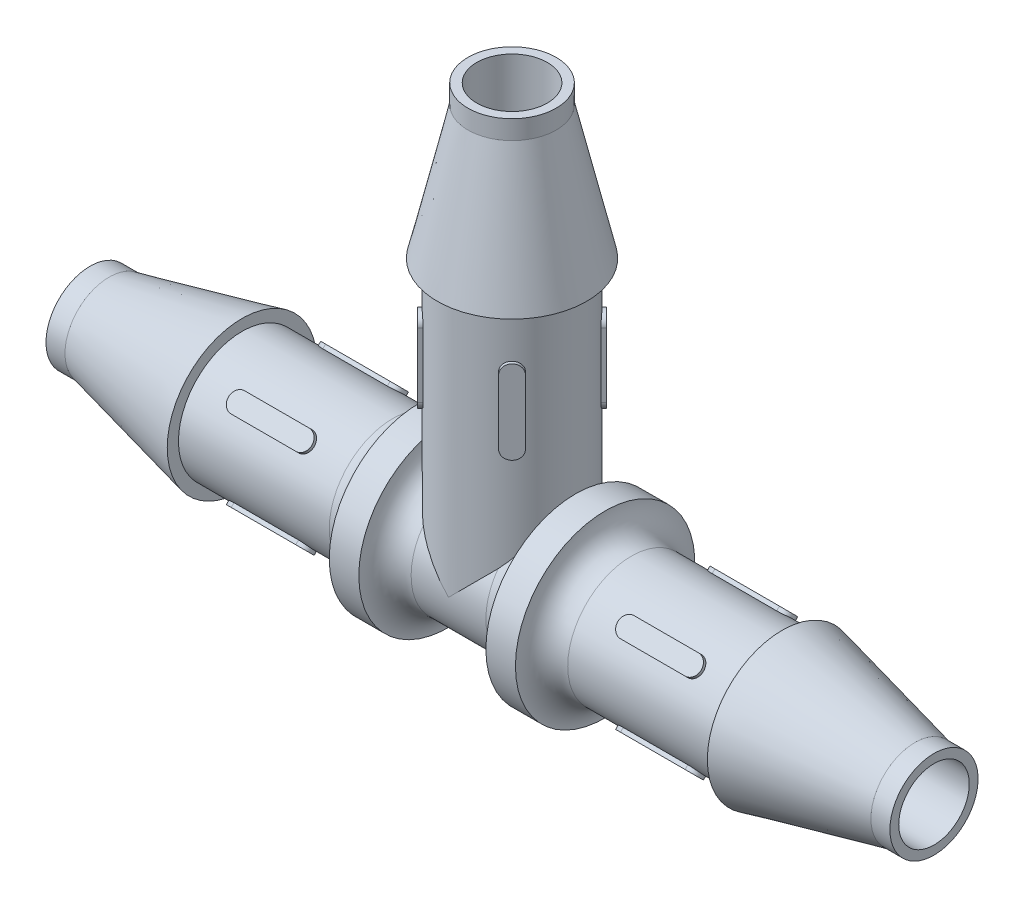
SolidWorks part; units mm, degrees
ref_plane "Front Plane" through (0, 0, 0) normal (0, 0, 1) x (1, 0, 0)
ref_plane "Top Plane" through (0, 0, 0) normal (0, 1, 0) x (1, 0, 0)
ref_plane "Right Plane" through (0, 0, 0) normal (1, 0, 0) x (0, 0, -1)
sketch "Sketch1" plane through (0, 0, 0) normal (0, 0, 1) x (1, 0, 0)
  line L0 (-17.78, 0) -> (17.78, 0) construction
  line L1 (17.78, 1.4859) -> (17.78, -1.4859) construction
  line L2 (17.78, 3.1496) -> (17.78, -3.1496) construction
  line L3 (17.78, 2.3812) -> (17.78, -2.3813) construction
  line L4 (0, 2.6772) -> (0, -2.6772) construction
  line L5 (0, -2.6772) -> (0, 17.4396) construction
  point P4 (0, 0)
  point P8 (17.78, 0)
  point P11 (17.78, 0)
  point P14 (17.78, 0)
  point P17 (0, 0)
  dimension "C" = 35.56
  dimension "A" = 2.9718
  dimension "B" = 6.2992
  dimension "For Tube ID" = 4.7625
  dimension "D1" = 5.3543
  dimension "D" = 20.1168
sketch "Sketch3" plane through (0, 0, 0) normal (0, 0, 1) x (1, 0, 0)
  line L0 (0, 0) -> (17.78, 0) construction
  line L1 (17.78, 1.4859) -> (17.78, 1.8574)
  line L2 (3.9218, -3.7795) -> (2.6772, -3.7795) construction
  line L3 (11.3792, 3.1496) -> (11.3792, 2.6772)
  line L4 (11.3792, 2.6772) -> (3.9218, 2.6772)
  line L5 (17.78, 1.8574) -> (16.9799, 1.8574)
  line L6 (3.9218, 2.6772) -> (3.9218, 3.7795)
  line L7 (3.9218, 3.7795) -> (2.6772, 3.7795)
  line L8 (2.6772, 3.7795) -> (2.6772, 2.6772)
  line L9 (2.6772, 2.6772) -> (0, 2.6772)
  line L10 (17.78, 1.4859) -> (0, 1.4859)
  line L11 (0, 1.4859) -> (0, 2.6772)
  line L12 (3.9218, 2.9134) -> (11.3792, 2.9134) construction
  line L13 (0, 0) -> (0, -2.6772) construction
  line L14 (16.9799, 1.8574) -> (11.3792, 3.1496)
  line L15 (3.9218, 17.4396) -> (0, 17.4396) construction
  line L16 (2.6772, -2.6772) -> (0, -2.6772) construction
  line L18 (11.3792, 3.1496) -> (17.78, 3.1496) construction
  dimension "D3" = 6.4008
  dimension "D8" = 0.8001
revolve "Revolve1" add sketch "Sketch3" angle 360 about L0
sketch "Sketch4" plane through (0, 0, 0) normal (0, 0, 1) x (1, 0, 0)
  line L0 (11.3792, 2.6772) -> (3.9218, 2.6772) construction
  line L1 (3.9218, 2.6772) -> (3.9218, 3.7795) construction
  line L2 (5.0241, 2.6772) -> (3.9218, 2.6772)
  line L3 (3.9218, 2.6772) -> (3.9218, 3.7795)
  line L4 (2.6772, 3.7795) -> (2.6772, 2.6772) construction
  line L5 (2.6772, 2.6772) -> (0, 2.6772) construction
  line L6 (2.6772, 3.7795) -> (2.6772, 2.6772)
  line L7 (2.6772, 2.6772) -> (1.5748, 2.6772)
  arc A0 (3.9218, 3.7795) -> (5.0241, 2.6772) centre (5.0241, 3.7795) ccw
  arc A1 (2.6772, 3.7795) -> (1.5748, 2.6772) centre (1.5748, 3.7795) cw
revolve "Revolve2" add sketch "Sketch4" angle 360 about L0
ref_plane "Plane1" through (0, 0, 0) normal (0, 0.7071, 0.7071) x (-1, 0, 0)
sketch "Sketch5" plane through (0, 0, 0) normal (0, 0.7071, 0.7071) x (-1, 0, 0)
  line L0 (0, 0) -> (-17.78, 0) construction
  line L1 (-6.8415, 0.4) -> (-9.5618, 0.4)
  line L2 (-6.8415, 0.4) -> (-6.8415, -0.4) construction
  line L3 (-6.8415, -0.4) -> (-9.5618, -0.4)
  line L4 (-9.5618, 0.4) -> (-9.5618, -0.4) construction
  line L5 (-5.0241, 2.6772) -> (-5.0241, 3.1496) construction
  line L6 (-5.0241, 3.1496) -> (-11.3792, 3.1496) construction
  line L7 (-11.3792, 3.1496) -> (-11.3792, 2.6772) construction
  line L8 (-8.2017, 3.1496) -> (-8.2017, 0.4) construction
  line L9 (-5.0241, 2.6772) -> (-6.4414, 2.6772) construction
  line L10 (-6.4414, 2.6772) -> (-6.4414, 0) construction
  line L11 (-11.3792, 2.6772) -> (-9.9619, 2.6772) construction
  line L12 (-9.9619, 2.6772) -> (-9.9619, 0) construction
  line L13 (-5.0241, 2.6772) -> (-11.3792, 2.6772) construction
  line L14 (-11.3792, -3.1496) -> (-11.3792, 3.1496) construction
  arc A0 (-9.5618, 0.4) -> (-9.5618, -0.4) centre (-9.5618, 0) ccw
  arc A1 (-6.8415, 0.4) -> (-6.8415, -0.4) centre (-6.8415, 0) cw
  dimension "D1" = 0.8001
  dimension "D2" = 3.5204
extrude "Extrude1" add sketch "Sketch5" along normal mid plane 5.622
pattern_circular "CirPattern1" count 2 every 90 about axis through (0, 0, 0) along (1, 0, 0) of "Extrude1"
sketch "Sketch6" plane through (17.78, 0, 0) normal (1, 0, 0) x (0, 0, -1)
  circle A0 centre (0, 0) radius 1.4859 construction
  circle A1 centre (0, 0) radius 1.4859
extrude "Cut-Extrude1" cut sketch "Sketch6" against normal through all
sketch "Sketch7" plane through (0, 0, 0) normal (0, 0, 1) x (1, 0, 0)
  line L0 (0, 0) -> (0, 15.346) construction
  line L1 (1.4859, 17.4396) -> (1.8574, 17.4396)
  line L2 (1.8574, 17.4396) -> (1.8574, 16.6395)
  line L3 (1.8574, 16.6395) -> (3.1496, 11.0388)
  line L4 (3.1496, 11.0388) -> (2.6772, 11.0388)
  line L5 (2.6772, 11.0388) -> (2.6772, 0)
  line L7 (1.4859, 17.4396) -> (1.4859, 0)
  line L8 (17.78, 1.4859) -> (17.78, 1.8574) construction
  line L9 (11.3792, 3.1496) -> (11.3792, 2.6772) construction
  line L10 (3.9218, 17.4396) -> (0, 17.4396) construction
  line L11 (2.6772, 0) -> (1.4859, 0)
  line L12 (0, 0) -> (17.78, 0) construction
  line L13 (17.78, 1.8574) -> (16.9799, 1.8574) construction
  dimension "D3" = 6.4008
  dimension "D1" = 2.9718
  dimension "D2" = 6.2992
revolve "Revolve3" add sketch "Sketch7" angle 360 about L0
mirror "Mirror1" about plane through (0, 0, 0) normal (1, 0, 0) of bodies 112 110
ref_plane "Plane2" through (0, 0, 0) normal (-0.7071, 0, 0.7071) x (0.7071, 0, 0.7071)
sketch "Sketch8" plane through (0, 0, 0) normal (-0.7071, 0, 0.7071) x (0.7071, 0, 0.7071)
  line L0 (0, 0) -> (0, 15.346) construction
  line L1 (-0.4001, 8.7694) -> (0.4001, 8.7694) construction
  line L2 (-0.4001, 8.7694) -> (-0.4, 6.049)
  line L3 (-0.4, 6.049) -> (0.4001, 6.049) construction
  line L4 (0.4001, 8.7694) -> (0.4001, 6.049)
  line L5 (-2.6772, 11.0388) -> (-2.6772, 3.7795) construction
  line L6 (-2.6772, 7.4092) -> (-0.4, 7.4092) construction
  line L7 (-2.6772, 11.0388) -> (-2.6772, 1.9589) construction
  arc A0 (-0.4001, 8.7694) -> (0.4001, 8.7694) centre (0, 8.7694) cw
  arc A1 (-0.4, 6.049) -> (0.4001, 6.049) centre (0, 6.049) ccw
  dimension "D1" = 3.5204
  dimension "D2" = 0.8001
extrude "Extrude2" add sketch "Sketch8" along normal mid plane 5.622
pattern_circular "CirPattern2" count 2 every 90 about axis through (0, 0, 0) along (0, 1, 0) of "Extrude2"
sketch "Sketch9" plane through (17.78, 0, 0) normal (1, 0, 0) x (0, 0, -1)
  circle A0 centre (0, 0) radius 1.4859 construction
  circle A1 centre (0, 0) radius 1.4859
extrude "Cut-Extrude2" cut sketch "Sketch9" against normal through all
sketch "Sketch10" plane through (0, 0, 0) normal (0, 1, 0) x (1, 0, 0)
  circle A0 centre (0, 0) radius 1.4859 construction
  circle A1 centre (0, 0) radius 1.4859
extrude "Cut-Extrude3" cut sketch "Sketch10" along normal through all
ref_axis "Axis1" through (8.7514, 0, 0) along (-1, 0, 0)
ref_axis "Axis2" through (0, 17.4396, 0) along (0, -1, 0)
ref_point "Point1"
ref_point "Point2"
ref_point "Point3"
equation "\"D1@Sketch3\"=\"A@Sketch1\"*1.25"
equation "\"D3@Sketch3\"=\"C@Sketch1\"*.18"
equation "\"D4@Sketch3\"=\"C@Sketch1\"*.035"
equation "\"D6@Sketch3\" = \"D2@Sketch3\"/2"
equation "\"D2@Sketch3\"=\"B@Sketch1\"*.85"
equation "\"D5@Sketch3\"=\"B@Sketch1\"*1.2"
equation "\"D8@Sketch3\" = \"D3@Sketch3\"/8"
equation "\"D1@Sketch5\" = \"D8@Sketch3\""
equation "\"D2@Sketch5\" = \"D3@Sketch3\"*.55"
equation "\"D1@Extrude1\" = \"D2@Sketch3\"*1.05"
equation "\"D1@Sketch7\" = \"A@Sketch1\""
equation "\"D2@Sketch7\"= \"B@Sketch1\""
equation "\"D3@Sketch7\" = \"D3@Sketch3\""
equation "\"D1@Sketch8\" = \"D2@Sketch5\""
equation "\"D2@Sketch8\" = \"D1@Sketch5\""
equation "\"D1@Extrude2\" = \"D1@Extrude1\""
equation "\"D1@Sketch1\"=\"B@Sketch1\"*.85"
